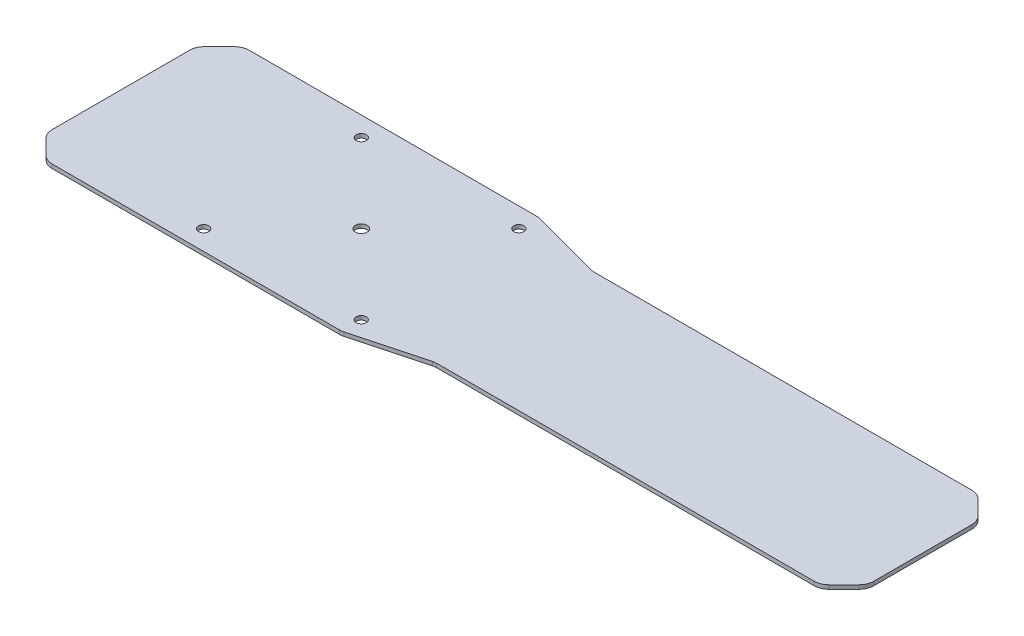
SolidWorks part; units mm, degrees
material "1060 Alloy"
ref_plane "Front Plane" through (0, 0, 0) normal (0, 0, 1) x (1, 0, 0)
ref_plane "Top Plane" through (0, 0, 0) normal (0, 1, 0) x (1, 0, 0)
ref_plane "Right Plane" through (0, 0, 0) normal (1, 0, 0) x (0, 0, -1)
sketch "Sketch1" plane through (0, 0, 0) normal (0, 1, 0) x (1, 0, 0)
  line L0 (40, -50) -> (77.3205, -40)
  line L1 (-40, 50) -> (40, 50)
  line L2 (-40, 50) -> (-40, -50) construction
  line L3 (-40, -50) -> (40, -50)
  line L4 (40, 50) -> (40, -50) construction
  line L5 (-40, 50) -> (40, -50) construction
  line L6 (-40, -50) -> (40, 50) construction
  line L7 (-40, 50) -> (-122, 50)
  line L8 (-40, 50) -> (-40, -50) construction
  line L9 (-40, -50) -> (-122, -50)
  line L10 (-122, 50) -> (-122, -50)
  line L12 (40, 50) -> (40, -50) construction
  line L14 (40, 50) -> (77.3205, 40)
  line L16 (77.3205, 40) -> (285, 40)
  line L17 (77.3205, 40) -> (77.3205, -40) construction
  line L18 (77.3205, -40) -> (285, -40)
  line L19 (285, 40) -> (285, -40)
  point P0 (0, 0)
  point P11 (250, 0)
  dimension "D1" = 80
  dimension "D2" = 100
  dimension "D5" = 250
  dimension "D4" = 75
  dimension "D6" = 75
  dimension "D7" = 80
  dimension "D8" = 35
  dimension "D3" = 82
extrude "Boss-Extrude2" add sketch "Sketch1" along normal blind 2
chamfer "Chamfer2" distance 12 angle 45 4 edges at (-122, 1, 50) (-122, 1, -50) (285, 1, -40) (285, 1, 40)
fillet "Fillet1" radius 7.5 12 edges at (-110, 1, -50) (-122, 1, -38) (-122, 1, 38) (-110, 1, 50) (273, 1, 40) (285, 1, 28) (285, 1, -28) (273, 1, -40) (40, 1, 50) (77.3205, 1, 40) (77.3205, 1, -40) (40, 1, -50)
sketch "Sketch2" plane through (0, 2, 0) normal (0, 1, 0) x (1, 0, 0)
  line L0 (0, 50) -> (0, -50) construction
  line L1 (39.0126, 50) -> (-106.8934, 50) construction
  line L2 (-106.8934, -50) -> (39.0126, -50) construction
  line L3 (-122, 0) -> (285, 0) construction
  line L4 (-122, 34.8934) -> (-122, -34.8934) construction
  line L5 (285, -24.8934) -> (285, 24.8934) construction
  circle A0 centre (-40, 40) radius 2.575
  circle A1 centre (40, 40) radius 2.575
  circle A2 centre (40, -40) radius 2.575
  circle A3 centre (-40, -40) radius 2.575
  circle A5 centre (0, 0) radius 3
  dimension "D3" = 5.15
  dimension "D6" = 6
  dimension "D1" = 40
  dimension "D2" = 40
extrude "Cut-Extrude1" cut sketch "Sketch2" against normal through all
equation "\"Elevator Guide Rod Distance\"= 80mm"
equation "\"Extra Spacing\"= 20mm"
equation "\"Plate Thickness\"= 2mm"
equation "\"D1@Sketch1\"=\"Elevator Guide Rod Distance\""
equation "\"D2@Sketch1\"=\"Elevator Guide Rod Distance\"+\"Extra Spacing\""
equation "\"Elevator Servo Offset\"= 75mm"
equation "\"Servo Width\"= 42mm"
equation "\"Pivot Point End Offset\"= 35mm"
equation "\"Origin Pivot Distance\"= 250mm"
equation "\"D5@Sketch1\"=\"Origin Pivot Distance\""
equation "\"Narrow Section Width\"= 80mm"
equation "\"D7@Sketch1\"=\"Narrow Section Width\""
equation "\"D8@Sketch1\"=\"Pivot Point End Offset\""
equation "\"D1@Sketch2\"=\"Elevator Guide Rod Distance\"/2"
equation "\"D2@Sketch2\"=\"Elevator Guide Rod Distance\"/2"
equation "\"Guide Rod Diameter\"= 5mm"
equation "\"D3@Sketch2\"=\"Guide Rod Diameter\"+.15"
equation "\"Servo Hole X-Offset\"= 15.5mm"
equation "\"Servo Hole Y-Offset\"= 15.5mm"
equation "\"D1\"= \"Servo Width\" / 2 + \"Extra Spacing\""
equation "\"Servo Shaft Diameter\"= 22.5mm"
equation "\"Elevator Screw Lift Diameter\"= 6mm"
equation "\"D6@Sketch2\"=\"Elevator Screw Lift Diameter\""
equation "\"D3@Sketch1\"= \"Servo Width\" + \"Extra Spacing\" * 2"
equation "\"D1@Boss-Extrude2\"=\"Plate Thickness\""
